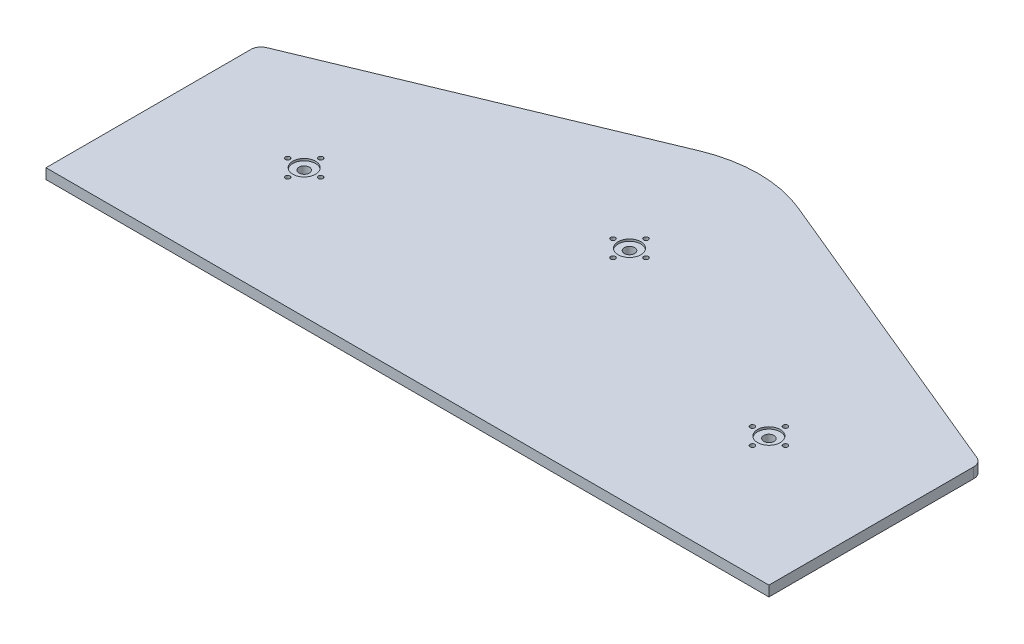
SolidWorks part; units mm, degrees
ref_plane "Plan de face" through (0, 0, 0) normal (0, 0, 1) x (1, 0, 0)
ref_plane "Plan de dessus" through (0, 0, 0) normal (0, 1, 0) x (1, 0, 0)
ref_plane "Plan de droite" through (0, 0, 0) normal (1, 0, 0) x (0, 0, -1)
sketch "Esquisse1" plane through (0, 0, 0) normal (0, 1, 0) x (1, 0, 0)
  line L0 (0, 122.4055) -> (0, -37.6593) construction
  line L1 (350, 0) -> (-350, 0)
  line L2 (-350, 0) -> (-350, 198.3248)
  line L3 (-343.8353, 207.5601) -> (-47.9412, 330.4411)
  line L4 (350, 0) -> (350, 198.3248)
  line L5 (343.8353, 207.5601) -> (47.9412, 330.4411)
  line L6 (-172.5198, 125) -> (148.2237, 125) construction
  circle A0 centre (0, 215) radius 5
  circle A1 centre (-225, 125) radius 5
  circle A2 centre (225, 125) radius 5
  circle A3 centre (0, 215) radius 19.7026 construction
  circle A4 centre (225, 125) radius 22.6514 construction
  circle A5 centre (-225, 125) radius 22.6514 construction
  arc A6 (47.9412, 330.4411) -> (-47.9412, 330.4411) centre (0, 215) ccw
  arc A7 (350, 198.3248) -> (343.8353, 207.5601) centre (340, 198.3248) ccw
  arc A8 (-350, 198.3248) -> (-343.8353, 207.5601) centre (-340, 198.3248) cw
  point P8 (0, 0)
  point P22 (350, 205)
  point P25 (-350, 205)
  dimension "D1" = 10
  dimension "D7" = 125
  dimension "D8" = 10
  dimension "D2" = 90
  dimension "D3" = 225
  dimension "D4" = 125
  dimension "D5" = 205
  dimension "D6" = 700
extrude "Boss.-Extru.1" add sketch "Esquisse1" along normal blind 10
sketch "Esquisse2" plane through (0, 10, 0) normal (0, 1, 0) x (1, 0, 0)
  circle A0 centre (0, 215) radius 11
  circle A1 centre (225, 125) radius 11
  circle A2 centre (-225, 125) radius 11
  circle A3 centre (225, 125) radius 5 construction
  dimension "D1" = 22
extrude "Enlèv. mat.-Extru.1" cut sketch "Esquisse2" against normal blind 2
ref_axis "Axe1" through (225, 8, -125) along (0, -1, 0)
ref_axis "Axe2" through (0, 8, -215) along (0, -1, 0)
ref_axis "Axe3" through (-225, 8, -125) along (0, -1, 0)
hole_wizard "Chambrage pour vis à tête hexagonale M41" positions "Esquisse5" profile "Esquisse6" counterbore size "M4" standard "ISO" end condition through all
sketch "Esquisse5" plane through (0, 0, 0) normal (0, -1, 0) x (-1, 0, 0)
  line L1 (-225, 152.6221) -> (-225, 91.1236) construction
  point P0 (-225, 141)
  dimension "D1" = 16
sketch "Esquisse6" plane through (225, 0, -141) normal (1, 0, 0) x (0, 0, -1)
  line L0 (0, 0) -> (0, 10)
  line L1 (0, 10) -> (2.25, 10)
  line L3 (2.25, 10) -> (2.25, 4.4)
  line L4 (2.25, 4.4) -> (4, 4.4)
  line L5 (4, 4.4) -> (4, 0)
  line L7 (4, 0) -> (0, 0)
  line L11 (0, -6.35) -> (0, 107.95) construction
  dimension "Diamètre du perçage jusqu'au prochain" = 4.5
  dimension "Profondeur du perçage jusqu'au prochain" = 10
  dimension "Diamètre du chambrage" = 8
  dimension "Profondeur du chambrage" = 4.4
pattern_circular "Répétition circulaire1" count 4 over 360 about axis through (225, 8, -125) along (0, -1, 0) of "Chambrage pour vis à tête hexagonale M41"
hole_wizard "Chambrage pour vis à tête hexagonale M42" positions "Esquisse7" profile "Esquisse8" counterbore size "M4" standard "ISO" end condition through all
sketch "Esquisse7" plane through (0, 0, 0) normal (0, -1, 0) x (-1, 0, 0)
  line L0 (0, 254.0329) -> (0, 168.053) construction
  point P0 (0, 231)
  dimension "D1" = 16
sketch "Esquisse8" plane through (0, 0, -231) normal (1, 0, 0) x (0, 0, -1)
  line L0 (0, 0) -> (0, 10)
  line L1 (0, 10) -> (2.25, 10)
  line L3 (2.25, 10) -> (2.25, 4.4)
  line L4 (2.25, 4.4) -> (4, 4.4)
  line L5 (4, 4.4) -> (4, 0)
  line L7 (4, 0) -> (0, 0)
  line L11 (0, -6.35) -> (0, 107.95) construction
  dimension "Diamètre du perçage jusqu'au prochain" = 4.5
  dimension "Profondeur du perçage jusqu'au prochain" = 10
  dimension "Diamètre du chambrage" = 8
  dimension "Profondeur du chambrage" = 4.4
hole_wizard "Chambrage pour vis à tête hexagonale M43" positions "Esquisse9" profile "Esquisse10" counterbore size "M4" standard "ISO" end condition through all
sketch "Esquisse9" plane through (0, 0, 0) normal (0, -1, 0) x (-1, 0, 0)
  line L0 (225, 161.2031) -> (225, 103.324) construction
  point P0 (225, 141)
  dimension "D1" = 16
sketch "Esquisse10" plane through (-225, 0, -141) normal (1, 0, 0) x (0, 0, -1)
  line L0 (0, 0) -> (0, 10)
  line L1 (0, 10) -> (2.25, 10)
  line L3 (2.25, 10) -> (2.25, 4.4)
  line L4 (2.25, 4.4) -> (4, 4.4)
  line L5 (4, 4.4) -> (4, 0)
  line L7 (4, 0) -> (0, 0)
  line L11 (0, -6.35) -> (0, 107.95) construction
  dimension "Diamètre du perçage jusqu'au prochain" = 4.5
  dimension "Profondeur du perçage jusqu'au prochain" = 10
  dimension "Diamètre du chambrage" = 8
  dimension "Profondeur du chambrage" = 4.4
pattern_circular "Répétition circulaire2" count 4 over 360 about axis through (0, 8, -215) along (0, -1, 0) of "Chambrage pour vis à tête hexagonale M42"
pattern_circular "Répétition circulaire3" count 4 over 360 about axis through (-225, 8, -125) along (0, -1, 0) of "Chambrage pour vis à tête hexagonale M43"
